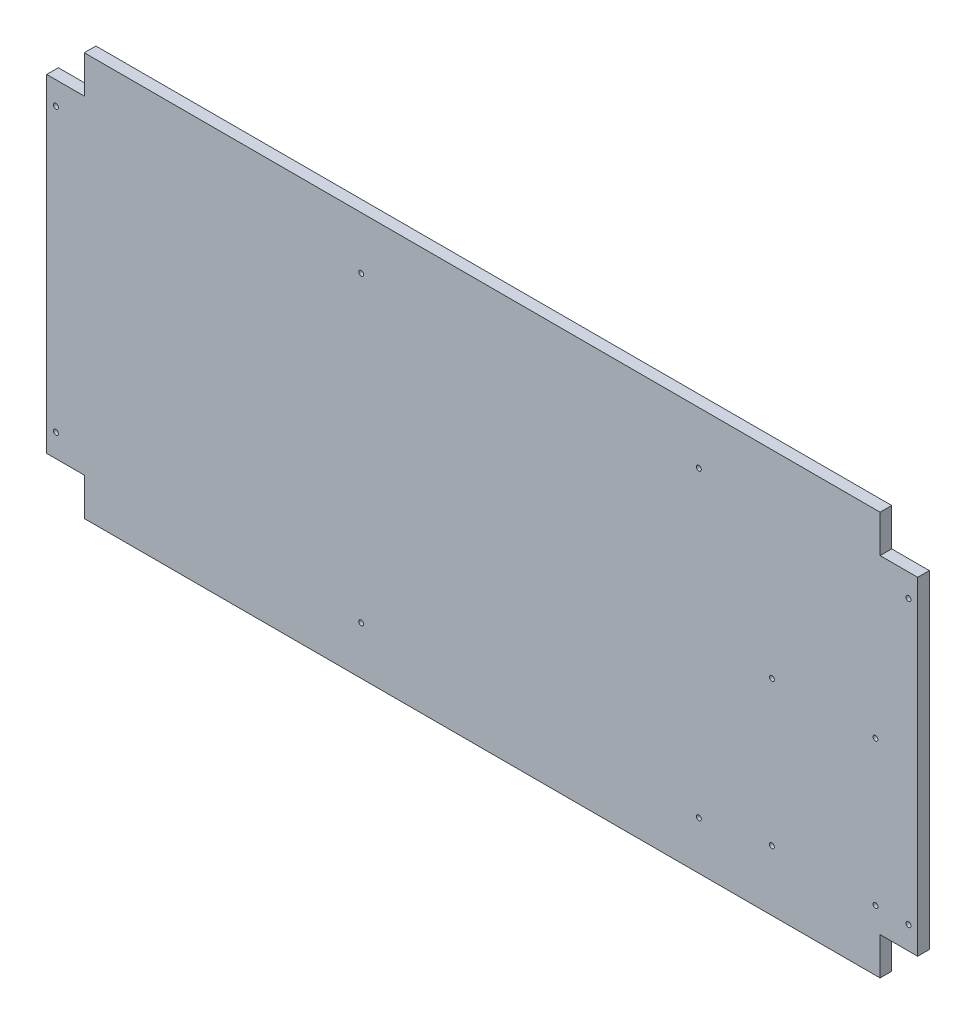
SolidWorks part; units mm, degrees
ref_plane "Front Plane" through (0, 0, 0) normal (0, 0, 1) x (1, 0, 0)
ref_plane "Top Plane" through (0, 0, 0) normal (0, 1, 0) x (1, 0, 0)
ref_plane "Right Plane" through (0, 0, 0) normal (1, 0, 0) x (0, 0, -1)
sketch "Sketch2" plane through (0, 0, 0) normal (0, 0, 1) x (1, 0, 0)
  line L1 (-475, -220) -> (475, -220)
  line L2 (-475, -220) -> (-475, 220)
  line L3 (-475, 220) -> (475, 220)
  line L4 (475, -220) -> (475, 220)
  line L5 (-475, -220) -> (475, 220) construction
  line L6 (-475, 220) -> (475, -220) construction
  point P0 (0, 0)
  dimension "D1" = 950
  dimension "D2" = 440
extrude "Boss-Extrude1" add sketch "Sketch2" along normal blind 12.7
sketch "Sketch3" plane through (0, 0, 12.7) normal (0, 0, 1) x (1, 0, 0)
  line L0 (0, 220) -> (0, -220) construction
  line L1 (-475, 220) -> (-434, 220)
  line L2 (-475, 220) -> (-475, 179)
  line L3 (-475, 179) -> (-434, 179)
  line L4 (-434, 220) -> (-434, 179)
  line L5 (-475, 220) -> (-434, 179) construction
  line L6 (-475, 179) -> (-434, 220) construction
  line L7 (475, 220) -> (-475, 220) construction
  line L8 (-475, -220) -> (475, -220) construction
  line L9 (-475, 0) -> (475, 0) construction
  line L10 (-475, 220) -> (-475, -220) construction
  line L11 (475, -220) -> (475, 220) construction
  line L12 (475, 179) -> (434, 220) construction
  line L13 (475, 220) -> (434, 179) construction
  line L14 (434, 220) -> (434, 179)
  line L15 (475, 179) -> (434, 179)
  line L16 (475, 220) -> (475, 179)
  line L17 (475, 220) -> (434, 220)
  line L18 (475, -220) -> (434, -179) construction
  line L19 (475, -179) -> (434, -220) construction
  line L20 (475, -220) -> (434, -220)
  line L21 (475, -220) -> (475, -179)
  line L22 (434, -220) -> (434, -179)
  line L23 (475, -179) -> (434, -179)
  line L24 (-475, -179) -> (-434, -220) construction
  line L25 (-475, -220) -> (-434, -179) construction
  line L26 (-434, -220) -> (-434, -179)
  line L27 (-475, -179) -> (-434, -179)
  line L28 (-475, -220) -> (-475, -179)
  line L29 (-475, -220) -> (-434, -220)
  point P4 (-454.5, 199.5)
  point P22 (454.5, 199.5)
  point P27 (454.5, -199.5)
  point P32 (-454.5, -199.5)
  dimension "D1" = 41
  dimension "D2" = 41
extrude "Cut-Extrude1" cut sketch "Sketch3" against normal up to next
sketch "Sketch4" plane through (0, 0, 12.7) normal (0, 0, 1) x (1, 0, 0)
  line L0 (-465, 179) -> (-465, -179) construction
  line L1 (-475, 179) -> (-434, 179) construction
  line L2 (-434, -179) -> (-475, -179) construction
  line L3 (0, 220) -> (0, -220) construction
  line L4 (434, 220) -> (-434, 220) construction
  line L5 (-434, -220) -> (434, -220) construction
  line L6 (0, 0) -> (-475, 0) construction
  line L7 (-475, 179) -> (-475, -179) construction
  circle A0 centre (-465, -154) radius 2.75
  circle A1 centre (-465, 154) radius 2.75
  circle A2 centre (465, -154) radius 2.75
  circle A3 centre (465, 154) radius 2.75
  dimension "D1" = 5.5
  dimension "D2" = 25
  dimension "D3" = 10
extrude "Cut-Extrude2" cut sketch "Sketch4" against normal up to next
sketch "Sketch6" plane through (0, 0, 12.7) normal (0, 0, 1) x (1, 0, 0)
  circle A0 centre (-131.9734, -167.5194) radius 2.665
  circle A1 centre (236.3266, -167.5194) radius 2.665
  circle A2 centre (236.3266, 162.6806) radius 2.665
  circle A3 centre (-131.9734, 162.6806) radius 2.665
  dimension "D1" = 5.33
extrude "Cut-Extrude3" cut sketch "Sketch6" against normal up to next
sketch "Sketch7" plane through (0, 0, 12.7) normal (0, 0, 1) x (1, 0, 0)
  circle A0 centre (429, 4) radius 2.665
  circle A1 centre (429, -154) radius 2.665
  circle A2 centre (316, 4) radius 2.665
  circle A3 centre (316, -154) radius 2.665
  dimension "D1" = 5.33
extrude "Cut-Extrude4" cut sketch "Sketch7" against normal up to next
